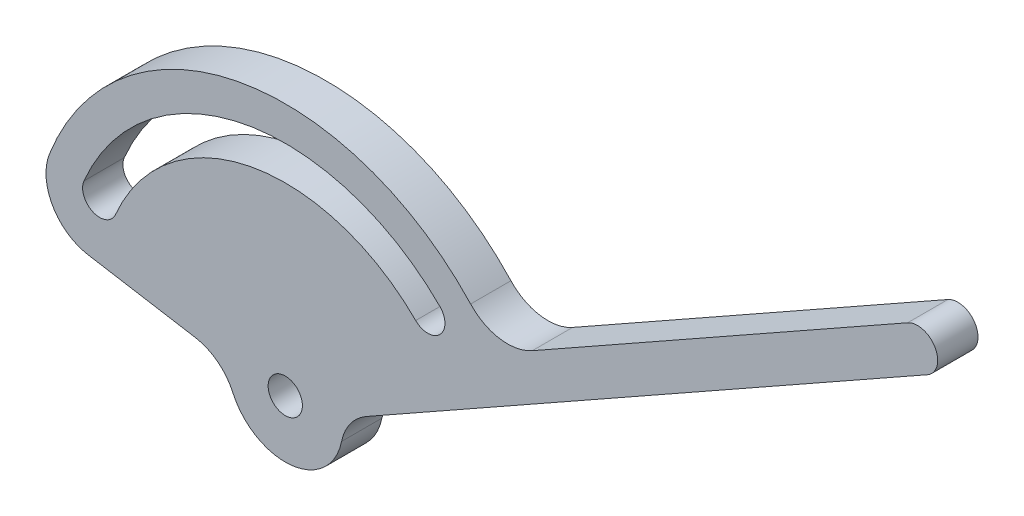
SolidWorks part; units mm, degrees
ref_plane "Front Plane" through (0, 0, 0) normal (0, 0, 1) x (1, 0, 0)
ref_plane "Top Plane" through (0, 0, 0) normal (0, 1, 0) x (1, 0, 0)
ref_plane "Right Plane" through (0, 0, 0) normal (1, 0, 0) x (0, 0, -1)
sketch "Sketch1" plane through (0, 0, 0) normal (0, 0, 1) x (1, 0, 0)
  line L0 (-1000, 0) -> (49000, 0) construction
  line L1 (17.9605, 17.9605) -> (0, 0) construction
  line L2 (-23.3808, 9.9246) -> (0, 0) construction
  circle A0 centre (0, 0) radius 2.159
  circle A2 centre (0, 0) radius 31.877
  arc A3 (17.9605, 17.9605) -> (-23.3808, 9.9246) centre (0, 0) ccw construction
  arc A4 (19.4872, 19.4872) -> (-25.3682, 10.7682) centre (0, 0) ccw
  arc A5 (16.4339, 16.4339) -> (-21.3935, 9.081) centre (0, 0) ccw
  arc A6 (16.4339, 16.4339) -> (19.4872, 19.4872) centre (17.9605, 17.9605) ccw
  arc A7 (-25.3682, 10.7682) -> (-21.3935, 9.081) centre (-23.3808, 9.9246) ccw
  point P6 (-4.8465, 24.9333)
  point P16 (-22.7016, 11.3929)
  dimension "D1" = 25.4
  dimension "D2" = 2.159
  dimension "D5" = 4.318
  dimension "D6" = 4.318
  dimension "D3" = 45
  dimension "D4" = 112
extrude "Boss-Extrude1" add sketch "Sketch1" along normal blind 5.08
sketch "Sketch2" plane through (0, 0, 5.08) normal (0, 0, 1) x (1, 0, 0)
  line L0 (0, 0) -> (17.9605, 17.9605) construction
  line L3 (-1000, 0) -> (49000, 0) construction
  line L4 (17.9605, 17.9605) -> (46.6973, 46.6973) construction
  line L7 (46.6973, 46.6973) -> (79.6721, 44.9692) construction
  line L8 (0, 0) -> (79.6721, 44.9692)
  line L9 (1.2485, -2.212) -> (80.9206, 42.7572)
  line L10 (-1.2485, 2.212) -> (78.4236, 47.1812)
  arc A0 (1.2485, -2.212) -> (-1.2485, 2.212) centre (0, 0) cw
  arc A1 (80.9206, 42.7572) -> (78.4236, 47.1812) centre (79.6721, 44.9692) ccw
  circle M3 centre (0, 0) radius 31.877
  dimension "D3" = 132
  dimension "D4" = 2.54
  dimension "D1" = 40.64
  dimension "D2" = 33.02
  dimension "D5" = 2.54
extrude "Boss-Extrude4" add sketch "Sketch2" against normal blind 5.08 contours L10 M3 region at (28.9448, 14.8478, 5.08)
sketch "Sketch6" plane through (0, 0, 5.08) normal (0, 0, 1) x (1, 0, 0)
  line L2 (28.9205, 13.4069) -> (7.1518, 1.12)
  line L3 (28.9205, 13.4069) -> (80.9206, 42.7572) construction
  line L4 (-7.239, 0) -> (-31.6127, 4.0963)
  line L7 (28.9205, 13.4069) -> (80.9206, 42.7572)
  line L8 (78.4236, 47.1812) -> (26.4235, 17.8309)
  line L9 (28.9205, 13.4069) -> (80.9206, 42.7572)
  line L10 (78.4236, 47.1812) -> (26.4235, 17.8309)
  circle A4 centre (0, 0) radius 7.239
  circle A5 centre (0, 0) radius 7.239
  arc A6 (26.4235, 17.8309) -> (28.9205, 13.4069) centre (0, 0) ccw construction
  arc A8 (-25.3682, 10.7682) -> (-21.3935, 9.081) centre (-23.3808, 9.9246) ccw construction
  arc A11 (26.4235, 17.8309) -> (28.9205, 13.4069) centre (0, 0) ccw
  arc A12 (80.9206, 42.7572) -> (78.4236, 47.1812) centre (79.6721, 44.9692) ccw
  arc A13 (26.4235, 17.8309) -> (28.9205, 13.4069) centre (0, 0) ccw
  arc A14 (80.9206, 42.7572) -> (78.4236, 47.1812) centre (79.6721, 44.9692) ccw
  point P13 (-31.6084, 4.1297)
  point P14 (0, 0)
  point P15 (-31.8573, 1.12)
  arc M5 (26.4235, 17.8309) -> (28.9205, 13.4069) centre (0, 0) ccw
  dimension "D2" = 7.112
  dimension "D1" = 5.08
  dimension "D3" = 0
extrude "Cut-Extrude1" cut sketch "Sketch6" against normal through all both and the other way through all contours A5 L4 L2 M5 region at (1.6833, -11.6773, 5.08)
fillet "Fillet2" radius 6.35 4 edges at (7.1518, 1.12, 2.54) (-7.239, 0, 2.54) (26.4235, 17.8309, 2.54) (-31.6127, 4.0963, 2.54)
